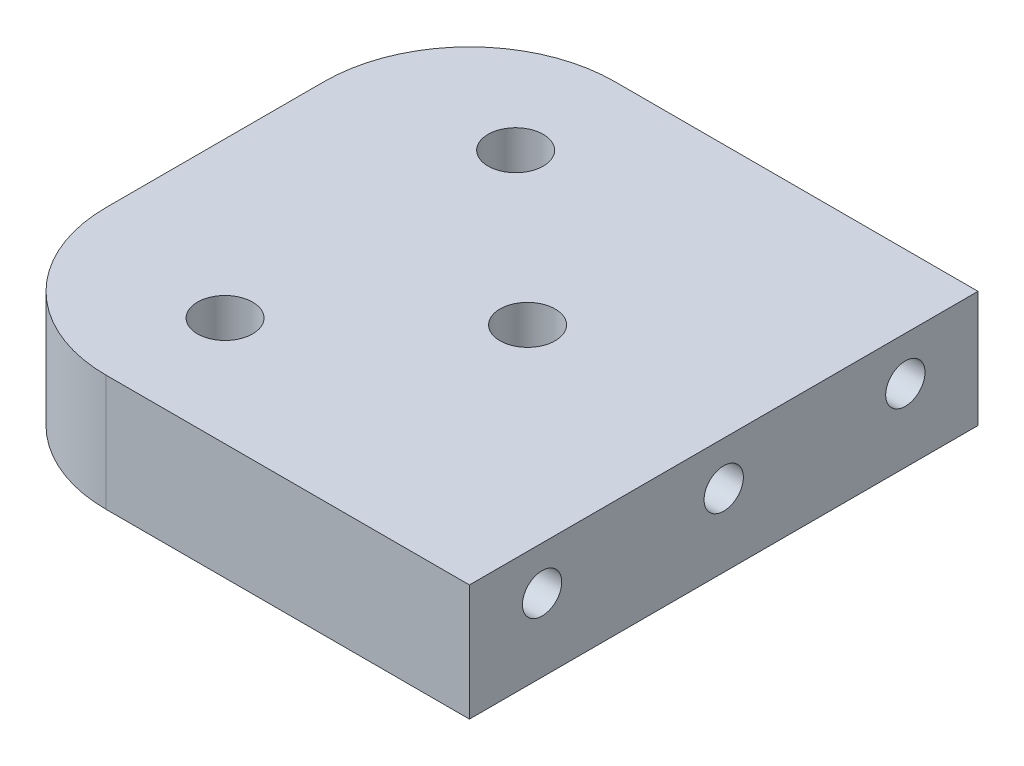
SolidWorks part; units mm, degrees
ref_plane "Front Plane" through (0, 0, 0) normal (0, 0, 1) x (1, 0, 0)
ref_plane "Top Plane" through (0, 0, 0) normal (0, 1, 0) x (1, 0, 0)
ref_plane "Right Plane" through (0, 0, 0) normal (1, 0, 0) x (0, 0, -1)
sketch "Sketch1" plane through (0, 0, 0) normal (0, 1, 0) x (1, 0, 0)
  line L1 (-17.5, 17.5) -> (17.5, 17.5)
  line L2 (-17.5, 17.5) -> (-17.5, -17.5)
  line L3 (-17.5, -17.5) -> (17.5, -17.5)
  line L4 (17.5, 17.5) -> (17.5, -17.5)
  line L5 (-17.5, 17.5) -> (17.5, -17.5) construction
  line L6 (-17.5, -17.5) -> (17.5, 17.5) construction
  point P0 (0, 0)
  dimension "D1" = 35
  dimension "D2" = 35
extrude "Boss-Extrude1" add sketch "Sketch1" along normal blind 8
hole_wizard "#6-32 Tapped Hole1" positions "Sketch2" profile "Sketch3" tap size "#6-32" standard "ANSI Inch"
sketch "Sketch2" plane through (17.5, 0, 0) normal (1, 0, 0) x (0, 0, -1)
  line L0 (-17.5, 0) -> (17.5, 0) construction
  line L1 (-17.5, 8) -> (-17.5, 0) construction
  line L2 (17.5, 8) -> (17.5, 0) construction
  point P0 (-12.5, 5)
  point P2 (0, 5)
  point P4 (12.5, 5)
  dimension "D1" = 5
  dimension "D2" = 5
  dimension "D3" = 5
cosmetic thread "Hole Thread1"
cosmetic thread "Hole Thread2"
cosmetic thread "Hole Thread3"
sketch "Sketch3" plane through (17.5, 5, 12.5) normal (0, 1, 0) x (0, 0, -1)
  line L0 (0, 0) -> (0, 10.2027)
  line L1 (0, 10.2027) -> (1.3525, 9.39)
  line L2 (1.3525, 9.39) -> (1.3525, 0)
  line L5 (1.3525, 0) -> (0, 0)
  line L10 (0, 10.2027) -> (-1.3525, 9.39) construction
  line L11 (0, -6.35) -> (0, 107.95) construction
  dimension "Tap Drill Dia." = 2.7051
  dimension "Tap Drill Depth" = 9.39
  dimension "Drill Angle" = 118
hole_wizard "#6 Clearance Hole1" positions "Sketch4" profile "Sketch5" hole size "#6" standard "ANSI Inch" end condition through all
sketch "Sketch4" plane through (0, 8, 0) normal (0, 1, 0) x (1, 0, 0)
  point P0 (4, 0)
  point P2 (-6.82, 10)
  point P4 (-6.82, -10)
  point P14 (0, 0)
  dimension "D1" = 10.82
  dimension "D2" = 10
  dimension "D3" = 10
  dimension "D4" = 4
sketch "Sketch5" plane through (4, 8, 0) normal (1, 0, 0) x (0, 0, 1)
  line L0 (0, 0) -> (0, 8)
  line L1 (0, 8) -> (1.8986, 8)
  line L2 (1.8986, 8) -> (1.8986, 0)
  line L5 (1.8986, 0) -> (0, 0)
  line L11 (0, -6.35) -> (0, 107.95) construction
  dimension "Thru Hole Dia." = 3.7973
  dimension "Thru Hole Depth" = 8
fillet "Fillet1" radius 10 2 edges at (-17.5, 4, 17.5) (-17.5, 4, -17.5)
equation "\"D3@Sketch2\"=\"D2@Sketch2\""
equation "\"D3@Sketch4\"=\"D2@Sketch4\""
